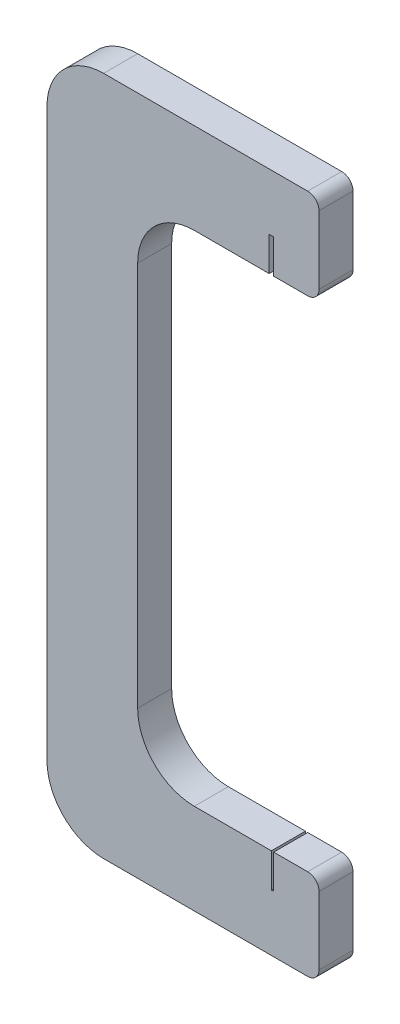
SolidWorks part; units mm, degrees
ref_plane "Front Plane" through (0, 0, 0) normal (0, 0, 1) x (1, 0, 0)
ref_plane "Top Plane" through (0, 0, 0) normal (0, 1, 0) x (1, 0, 0)
ref_plane "Right Plane" through (0, 0, 0) normal (1, 0, 0) x (0, 0, -1)
sketch "Sketch1" plane through (0, 0, 0) normal (0, 0, 1) x (1, 0, 0)
  line L0 (0, 55) -> (0, 5)
  line L1 (5, 0) -> (23, 0)
  line L2 (24, 1) -> (24, 7)
  line L3 (23, 8) -> (13, 8)
  line L4 (8, 13) -> (8, 47)
  line L5 (13, 52) -> (23, 52)
  line L6 (24, 53) -> (24, 59)
  line L7 (23, 60) -> (5, 60)
  arc A0 (5, 60) -> (0, 55) centre (5, 55) ccw
  arc A1 (13, 52) -> (8, 47) centre (13, 47) ccw
  arc A2 (13, 8) -> (8, 13) centre (13, 13) cw
  arc A3 (5, 0) -> (0, 5) centre (5, 5) cw
  arc A4 (24, 59) -> (23, 60) centre (23, 59) ccw
  arc A5 (24, 53) -> (23, 52) centre (23, 53) cw
  arc A6 (24, 1) -> (23, 0) centre (23, 1) cw
  arc A7 (24, 7) -> (23, 8) centre (23, 7) ccw
  point P11 (0, 60)
  point P18 (0, 0)
  point P21 (24, 60)
  point P24 (24, 52)
  point P27 (24, 0)
  point P30 (24, 8)
  dimension "D6" = 5
  dimension "D7" = 5
  dimension "D8" = 5
  dimension "D9" = 5
  dimension "D10" = 1
  dimension "D1" = 60
  dimension "D2" = 8
  dimension "D3" = 8
  dimension "D4" = 16
  dimension "D5" = 8
extrude "Boss-Extrude1" add sketch "Sketch1" along normal blind 3
sketch "Sketch3" plane through (0, 8, 0) normal (0, 1, 0) x (1, 0, 0)
  line L0 (0, -1.5) -> (19.9, -1.5) construction
  line L1 (0, -3) -> (0, 0) construction
  line L2 (23, 0) -> (13, 0) construction
  line L3 (19.8, -3) -> (20, -3)
  line L4 (19.8, -3) -> (19.8, 0)
  line L5 (19.8, 0) -> (20, 0)
  line L6 (20, -3) -> (20, 0)
  line L7 (19.8, -3) -> (20, 0) construction
  line L8 (19.8, 0) -> (20, -3) construction
  dimension "D1" = 19.9
  dimension "D2" = 0.2
extrude "Cut-Extrude1" cut sketch "Sketch3" against normal blind 3
sketch "Sketch4" plane through (0, 52, 0) normal (0, -1, 0) x (1, 0, 0)
  line L0 (0, 1.5) -> (19.8, 1.5) construction
  line L1 (0, 3) -> (0, 0) construction
  line L2 (13, 3) -> (23, 3) construction
  line L3 (19.6, 0) -> (20, 0)
  line L4 (19.6, 0) -> (19.6, 3)
  line L5 (19.6, 3) -> (20, 3)
  line L6 (20, 0) -> (20, 3)
  line L7 (19.6, 0) -> (20, 3) construction
  line L8 (19.6, 3) -> (20, 0) construction
  dimension "D1" = 19.8
  dimension "D2" = 0.4
extrude "Cut-Extrude2" cut sketch "Sketch4" against normal blind 3
equation "\"A.L\"= 0.07m"
equation "\"A.h\"= 0.007m"
equation "\"A.d\"= 0.003m"
equation "\"A.delta\"= 45.0001"
equation "\"A.w\"= 0.02m"
equation "\"A.v\"= 0.03m"
equation "\"A.s\"= 0.014m"
equation "\"A.t\"= 0.007m"
equation "\"B.L\"= 0.065m"
equation "\"B.h\"= 0.008m"
equation "\"B.s\"= 0.016m"
equation "\"B.t\"= 0.008m"
equation "\"C.h\"= 0.0065m"
equation "\"C.d\"= 0.003m"
equation "\"C.L\"= 0.05m"
equation "\"C.wmax\"= 0.005m"
equation "\"D.L\"= 0.06m"
equation "\"D.h\"= 0.008m"
equation "\"D.s\"= 0.012m"
equation "\"D.t\"= 0.008m"
equation "\"a_h\"= 0.0002m"
equation "\"a_d\"= 0.003m"
equation "\"a_L\"= 0.008m"
equation "\"b_h\"= 0.0004m"
equation "\"b_d\"= 0.003m"
equation "\"b_L\"= 0.007m"
equation "\"c_h\"= 0.0001m"
equation "\"c_d\"= 0.003m"
equation "\"c_L\"= 0.01m"
equation "\"d_h\"= 0.0001m"
equation "\"d_d\"= 0.003m"
equation "\"d_L\"= 0.01m"
equation "\"S.h\"= 0.015m"
equation "\"S.L\"= 0.09075m"
equation "\"D1@Sketch1\"=\"D.L\""
equation "\"D2@Sketch1\"=\"D.h\""
equation "\"D3@Sketch1\"=\"D.h\""
equation "\"D4@Sketch1\"=\"D.s\"+0.004"
equation "\"D5@Sketch1\"=\"D.h\""
equation "\"D1@Boss-Extrude1\"=\"A.d\""
equation "\"D1@Sketch3\"=\"D.h\"+\"D.s\"-\"a_h\"/2"
equation "\"D2@Sketch3\"=\"a_h\""
equation "\"D1@Sketch4\"=\"D.h\"+\"D.s\"-\"b_h\"/2"
equation "\"D2@Sketch4\"=\"b_h\""
